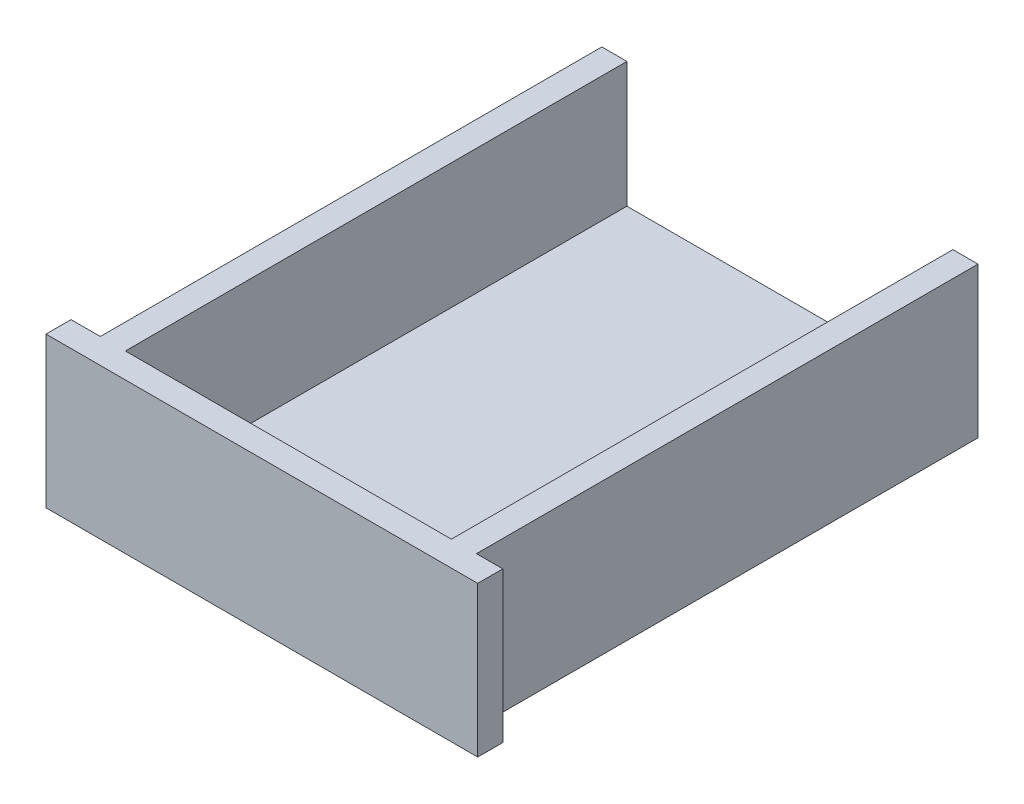
SolidWorks part; units mm, degrees
ref_plane "Front Plane" through (0, 0, 0) normal (0, 0, 1) x (1, 0, 0)
ref_plane "Top Plane" through (0, 0, 0) normal (0, 1, 0) x (1, 0, 0)
ref_plane "Right Plane" through (0, 0, 0) normal (1, 0, 0) x (0, 0, -1)
sketch "Sketch3" plane through (0, 0.0003, -31.967) normal (0, 0, 1) x (1, 0, 0)
  line L0 (106.7306, 145.4577) -> (106.7306, 86.6568) construction
  line L3 (99.2306, 85.6568) -> (114.2306, 85.6568)
  line L6 (100.2306, 86.6568) -> (113.2306, 86.6568)
  line L10 (99.2306, 85.6568) -> (99.2306, 91.6568)
  line L11 (99.2306, 91.6568) -> (100.2306, 91.6568)
  line L12 (100.2306, 86.6568) -> (100.2306, 91.6568)
  line L14 (114.2306, 85.6568) -> (114.2306, 91.6568)
  line L15 (114.2306, 91.6568) -> (113.2306, 91.6568)
  line L16 (113.2306, 86.6568) -> (113.2306, 91.6568)
  dimension "D3" = 1
  dimension "D5" = 1
  dimension "D6" = 5
extrude "Boss-Extrude1" add sketch "Sketch3" along normal up to surface (20 mm away)
sketch "Sketch4" plane through (0, 0.0001, -11.967) normal (0, 0, 1) x (1, 0, 0)
  line L0 (114.4806, 91.6568) -> (116.0806, 91.6568) construction
  line L1 (98.0647, 91.6568) -> (115.2806, 91.6568)
  line L2 (98.0647, 91.6568) -> (98.0647, 85.6568)
  line L3 (98.0647, 85.6568) -> (115.2806, 85.6568)
  line L4 (115.2806, 91.6568) -> (115.2806, 85.6568)
  line L8 (114.4806, 145.4575) -> (114.4806, 71.6475) construction
  line L14 (116.0806, 145.4575) -> (116.0806, 71.6475) construction
  line L15 (97.3806, 91.6568) -> (98.9806, 91.6568) construction
  line L16 (114.2306, 85.6568) -> (99.2306, 85.6568) construction
  line L17 (97.3806, 145.4576) -> (97.3806, 71.6476) construction
  line L18 (98.9806, 145.4576) -> (98.9806, 71.6476) construction
  line L22 (99.2306, 91.6568) -> (100.2306, 91.6568) construction
extrude "Boss-Extrude2" add sketch "Sketch4" along normal blind 1
sketch "Sketch6" plane through (0, 0.0001, -10.967) normal (0, 0, 1) x (1, 0, 0)
  line L0 (98.0647, 88.6568) -> (115.2806, 88.6568) construction
  line L1 (98.0647, 91.6568) -> (98.0647, 85.6568) construction
  line L2 (115.2806, 85.6568) -> (115.2806, 91.6568) construction
  line L3 (106.6727, 91.6568) -> (106.6727, 85.6568) construction
  line L4 (115.2806, 91.6568) -> (98.0647, 91.6568) construction
  line L5 (98.0647, 85.6568) -> (115.2806, 85.6568) construction
  line L6 (98.0647, 90.1568) -> (115.2806, 90.1568) construction
  line L7 (98.0647, 91.6568) -> (98.0647, 85.6568) construction
  line L8 (115.2806, 85.6568) -> (115.2806, 91.6568) construction
  dimension "D1" = 1.5
